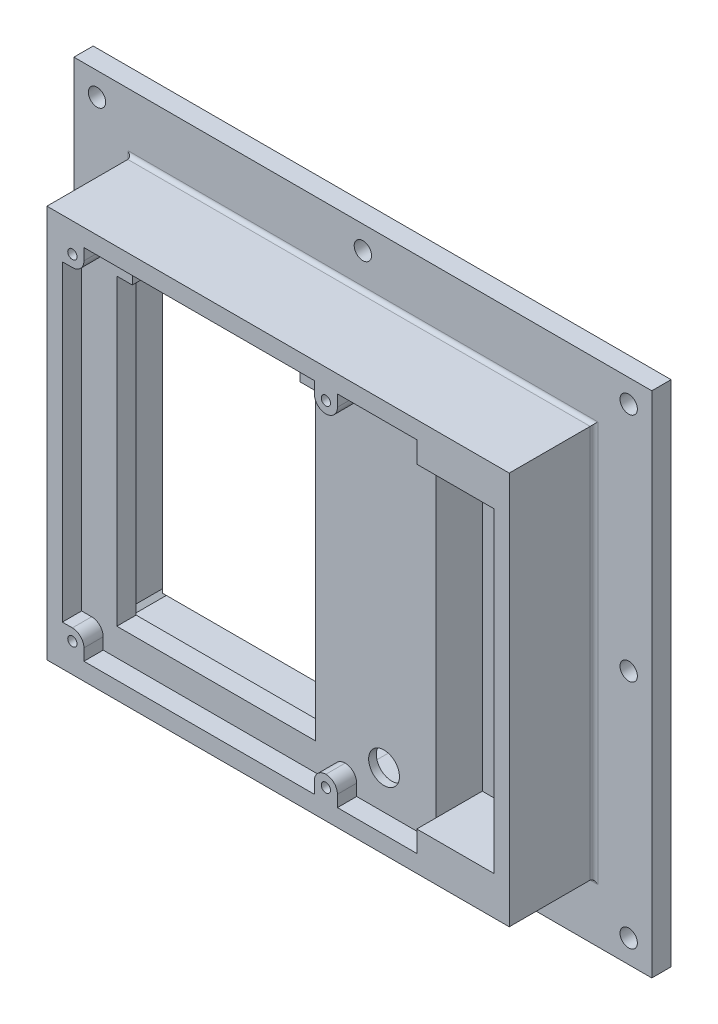
SolidWorks part; units mm, degrees
material "PBT Общее назначение"
ref_plane "Спереди" through (0, 0, 0) normal (0, 0, 1) x (1, 0, 0)
ref_plane "Сверху" through (0, 0, 0) normal (0, 1, 0) x (1, 0, 0)
ref_plane "Справа" through (0, 0, 0) normal (1, 0, 0) x (0, 0, -1)
sketch "Эскиз1" plane through (0, 0, 0) normal (0, 0, 1) x (1, 0, 0)
  line L0 (0, 0) -> (120, 0)
  line L1 (0, 0) -> (0, 102)
  line L2 (120, 0) -> (120, 102)
  line L3 (0, 102) -> (120, 102)
  dimension "D1" = 102
  dimension "D2" = 120
extrude "Бобышка-Вытянуть1" add sketch "Эскиз1" along normal blind 22
sketch "Эскиз2" plane through (0, 0, 22) normal (0, 0, 1) x (1, 0, 0)
  line L0 (4, 98) -> (116, 98)
  line L1 (4, 98) -> (4, 4)
  line L2 (116, 98) -> (116, 4)
  line L3 (4, 4) -> (116, 4)
  line L4 (60, 102) -> (60, 0) construction
  line L5 (120, 102) -> (0, 102) construction
  line L6 (0, 0) -> (120, 0) construction
  line L7 (120, 51) -> (0, 51) construction
  line L8 (120, 0) -> (120, 102) construction
  line L9 (0, 102) -> (0, 0) construction
  line L10 (60, 98) -> (60, 4) construction
  line L11 (116, 51) -> (4, 51) construction
  dimension "D1" = 94
  dimension "D2" = 112
extrude "Вырез-Вытянуть1" cut sketch "Эскиз2" against normal through all
sketch "Эскиз3" plane through (0, 0, 0) normal (0, 0, -1) x (-1, 0, 0)
  line L0 (-135, 117) -> (15, 117)
  line L1 (-135, 117) -> (-135, -15)
  line L2 (15, 117) -> (15, -15)
  line L3 (-135, -15) -> (15, -15)
  line L4 (0, 0) -> (-120, 0) construction
  line L5 (0, 102) -> (0, 0) construction
  line L6 (-120, 0) -> (-120, 102) construction
  line L7 (-120, 102) -> (0, 102) construction
  line L12 (-116, 98) -> (-4, 98) construction
  line L13 (-4, 98) -> (-4, 4) construction
  line L14 (-4, 4) -> (-116, 4) construction
  line L15 (-116, 4) -> (-116, 98) construction
  line L16 (-116, 98) -> (-4, 98)
  line L17 (-4, 98) -> (-4, 4)
  line L18 (-4, 4) -> (-116, 4)
  line L19 (-116, 4) -> (-116, 98)
  dimension "D1" = 15
  dimension "D2" = 15
  dimension "D3" = 15
  dimension "D4" = 15
extrude "Бобышка-Вытянуть2" add sketch "Эскиз3" along normal blind 5
sketch "Эскиз4" plane through (0, 0, 22) normal (0, 0, 1) x (1, 0, 0)
  line L0 (4, 98) -> (116, 98)
  line L1 (4, 98) -> (4, 83)
  line L2 (116, 98) -> (116, 83)
  line L3 (4, 83) -> (116, 83)
  line L4 (4, 19) -> (116, 19)
  line L5 (116, 4) -> (116, 19)
  line L7 (4, 4) -> (4, 19)
  line L8 (4, 98) -> (4, 4) construction
  line L9 (4, 4) -> (116, 4)
  line L12 (116, 51) -> (4, 51) construction
  line L13 (116, 4) -> (116, 98) construction
  dimension "D1" = 15
extrude "Бобышка-Вытянуть3" add sketch "Эскиз4" against normal blind 5
sketch "Эскиз5" plane through (0, 0, -5) normal (0, 0, -1) x (-1, 0, 0)
  line L0 (-60, 117) -> (-60, -15) construction
  line L1 (15, 117) -> (-135, 117) construction
  line L2 (-135, -15) -> (15, -15) construction
  line L3 (-135, 51) -> (15, 51) construction
  line L4 (-135, 117) -> (-135, -15) construction
  line L5 (15, -15) -> (15, 117) construction
ref_plane "Плоскость1" through (60, 0, 0) normal (1, 0, 0) x (0, -1, 0)
ref_plane "Плоскость2" through (0, 51, 0) normal (0, -1, 0) x (-1, 0, 0)
sketch "Эскиз6" plane through (0, 0, 17) normal (0, 0, -1) x (-1, 0, 0)
  line L0 (-4, 98) -> (-4, 83) construction
  line L1 (-116, 98) -> (-4, 98) construction
  line L2 (-4, 4) -> (-116, 4) construction
  line L3 (-4, 19) -> (-4, 4) construction
  line L4 (-6.6, 94.5) -> (-6.6, 7.5) construction
  line L5 (-6.6, 94.5) -> (-72.4, 94.5) construction
  line L6 (-6.6, 7.5) -> (-72.4, 7.5) construction
  line L7 (-72.4, 94.5) -> (-72.4, 7.5) construction
  circle A1 centre (-6.6, 94.5) radius 1.2
  circle A3 centre (-72.4, 94.5) radius 1.2
  circle A5 centre (-6.6, 7.5) radius 1.2
  circle A7 centre (-72.4, 7.5) radius 1.2
  dimension "D1" = 2.6
  dimension "D2" = 3.5
  dimension "D3" = 2.4
  dimension "D4" = 3.5
  dimension "D5" = 2.6
  dimension "D6" = 2.4
  dimension "D7" = 65.8
  dimension "D8" = 2.4
  dimension "D9" = 2.4
extrude "Вырез-Вытянуть2" cut sketch "Эскиз6" against normal through all
fillet "Скругление1" radius 1 4 edges at (60, 0, 0) (120, 51, 0) (60, 102, 0) (0, 51, 0)
sketch "Эскиз7" plane through (0, 0, 0) normal (0, 0, 1) x (1, 0, 0)
  line L0 (-9, -9) -> (-9, 111) construction
  line L1 (-9, -9) -> (129, -9) construction
  line L2 (-9, 111) -> (129, 111) construction
  line L3 (129, -9) -> (129, 111) construction
  line L4 (-15, -15) -> (-15, 117) construction
  line L5 (135, -15) -> (-15, -15) construction
  line L6 (-15, 117) -> (135, 117) construction
  line L7 (135, 117) -> (135, -15) construction
  circle A0 centre (-9, 111) radius 2.25
  circle A1 centre (129, 111) radius 2.25
  circle A2 centre (129, -9) radius 2.25
  circle A3 centre (-9, -9) radius 2.25
  circle A4 centre (-9, 51) radius 2.25
  circle A5 centre (60, 111) radius 2.25
  circle A6 centre (129, 51) radius 2.25
  circle A7 centre (60, -9) radius 2.25
  dimension "D5" = 4.5
  dimension "D6" = 4.5
  dimension "D7" = 4.5
  dimension "D8" = 4.5
  dimension "D9" = 4.5
  dimension "D10" = 4.5
  dimension "D11" = 4.5
  dimension "D12" = 4.5
  dimension "D13" = 60
  dimension "D1" = 6
  dimension "D2" = 6
  dimension "D3" = 6
  dimension "D4" = 6
extrude "Вырез-Вытянуть3" cut sketch "Эскиз7" against normal through all
sketch "Эскиз8" plane through (0, 0, 17) normal (0, 0, -1) x (-1, 0, 0)
  line L0 (-116, 4) -> (-92, 4)
  line L1 (-116, 4) -> (-116, 98)
  line L2 (-92, 4) -> (-92, 98)
  line L3 (-116, 98) -> (-92, 98)
  line L4 (-4, 4) -> (-116, 4) construction
  line L5 (-116, 98) -> (-4, 98) construction
  dimension "D1" = 24
extrude "Бобышка-Вытянуть4" add sketch "Эскиз8" along normal blind 15
sketch "Эскиз9" plane through (0, 0, 22) normal (0, 0, 1) x (1, 0, 0)
  line L1 (92, 19) -> (92, 83) construction
  line L2 (96, 92) -> (116, 92)
  line L3 (92, 19) -> (92, 83) construction
  line L4 (116, 92) -> (116, 10)
  line L5 (96, 10) -> (116, 10)
  line L6 (116, 19) -> (116, 83) construction
  line L7 (120, 102) -> (0, 102) construction
  line L8 (0, 0) -> (120, 0) construction
  line L9 (96, 92) -> (96, 10)
  dimension "D1" = 10
  dimension "D2" = 10
  dimension "D3" = 4
extrude "Вырез-Вытянуть4" cut sketch "Эскиз9" against normal blind 17
sketch "Эскиз10" plane through (0, 0, 2) normal (0, 0, -1) x (-1, 0, 0)
  line L0 (-106, 80) -> (-106, 55) construction
  line L1 (-116, 92) -> (-96, 92) construction
  line L3 (-116, 98) -> (-116, 4) construction
  circle A0 centre (-106, 80) radius 4
  circle A1 centre (-106, 55) radius 4
  dimension "D1" = 8
  dimension "D2" = 8
  dimension "D3" = 12
  dimension "D4" = 25
  dimension "D5" = 10
extrude "Вырез-Вытянуть5" cut sketch "Эскиз10" against normal through all
sketch "Эскиз11" plane through (0, 0, 5) normal (0, 0, 1) x (1, 0, 0)
  line L0 (99.5, 38.5) -> (113, 38.5)
  line L1 (99.5, 38.5) -> (99.5, 20)
  line L2 (113, 38.5) -> (113, 20)
  line L3 (99.5, 20) -> (113, 20)
  line L5 (96, 10) -> (116, 10) construction
  line L6 (116, 10) -> (116, 92) construction
  line L7 (96, 92) -> (96, 10) construction
  dimension "D1" = 18.5
  dimension "D2" = 13.5
  dimension "D3" = 10
  dimension "D4" = 3
  dimension "D5" = 3.5
extrude "Вырез-Вытянуть6" cut sketch "Эскиз11" against normal through all
sketch "Sketch1" plane through (0, 0, 22) normal (0, 0, 1) x (1, 0, 0)
  line L0 (3.6, 10.5) -> (3.6, 91.5)
  line L1 (9.6, 4.5) -> (69.4, 4.5)
  line L2 (9.6, 97.5) -> (69.4, 97.5)
  line L3 (75.4, 10.5) -> (75.4, 91.5)
  line L4 (69.4, 7.5) -> (69.4, 4.5)
  line L5 (72.4, 10.5) -> (75.4, 10.5)
  line L6 (6.6, 10.5) -> (3.6, 10.5)
  line L7 (9.6, 7.5) -> (9.6, 4.5)
  line L8 (6.6, 91.5) -> (3.6, 91.5)
  line L9 (9.6, 94.5) -> (9.6, 97.5)
  line L10 (69.4, 94.5) -> (69.4, 97.5)
  line L11 (72.4, 91.5) -> (75.4, 91.5)
  arc A0 (72.4, 10.5) -> (69.4, 7.5) centre (72.4, 7.5) ccw
  arc A1 (9.6, 7.5) -> (6.6, 10.5) centre (6.6, 7.5) ccw
  arc A2 (6.6, 91.5) -> (9.6, 94.5) centre (6.6, 94.5) ccw
  arc A3 (69.4, 94.5) -> (72.4, 91.5) centre (72.4, 94.5) ccw
  dimension "D1" = 6
  dimension "D2" = 6
  dimension "D3" = 6
  dimension "D4" = 6
extrude "Cut-Extrude1" cut sketch "Sketch1" against normal through all
sketch "Sketch2" plane through (0, 0, 22) normal (0, 0, 1) x (1, 0, 0)
  line L0 (75.4, 97.5) -> (96, 97.5)
  line L1 (75.4, 97.5) -> (75.4, 4.5)
  line L2 (96, 97.5) -> (96, 4.5)
  line L3 (75.4, 4.5) -> (96, 4.5)
  line L4 (75.4, 83) -> (75.4, 91.5) construction
  line L5 (69.4, 97.5) -> (9.6, 97.5) construction
  line L6 (9.6, 4.5) -> (69.4, 4.5) construction
  line L7 (96, 92) -> (96, 83) construction
extrude "Cut-Extrude2" cut sketch "Sketch2" against normal up to surface (5 mm away) up to face at (94, 51, 17)
fillet "Fillet1" radius 3 2 edges at (75.4, 91.5, 19.5) (75.4, 10.5, 19.5)
sketch "Sketch3" plane through (3.6, 0, 0) normal (1, 0, 0) x (0, 0, -1)
  line L4 (-22, 91.5) -> (-22, 10.5)
  line L5 (-22, 10.5) -> (5, 10.5)
  line L6 (5, 10.5) -> (5, 91.5)
  line L7 (5, 91.5) -> (-22, 91.5)
  line L8 (-22, 91.5) -> (-22, 10.5)
  line L9 (-22, 10.5) -> (5, 10.5)
  line L10 (5, 10.5) -> (5, 91.5)
  line L11 (5, 91.5) -> (-22, 91.5)
  dimension "D1" = 0
extrude "Boss-Extrude1" add sketch "Sketch3" along normal up to surface (0.4 mm away) up to face at (4, 94.75, 6)
sketch "Sketch4" plane through (0, 0, 17) normal (0, 0, -1) x (-1, 0, 0)
  line L0 (-4, 98) -> (-4, 4)
  line L1 (-4, 98) -> (-92, 98)
  line L2 (-4, 4) -> (-92, 4)
  line L3 (-92, 98) -> (-92, 4)
  line L4 (-4, 4) -> (-92, 4) construction
extrude "Boss-Extrude2" add sketch "Sketch4" along normal blind 6
sketch "Sketch5" plane through (0, 0, 17) normal (0, 0, 1) x (1, 0, 0)
  line L4 (64.4, 90.1) -> (13.4, 90.1)
  line L5 (64.4, 11.9) -> (64.4, 90.1)
  line L6 (13.4, 11.9) -> (64.4, 11.9)
  line L7 (13.4, 90.1) -> (13.4, 11.9)
  line L8 (64.4, 90.1) -> (13.4, 90.1) construction
  line L9 (64.4, 11.9) -> (64.4, 90.1) construction
  line L10 (13.4, 11.9) -> (64.4, 11.9) construction
  line L11 (13.4, 90.1) -> (13.4, 11.9) construction
  line L12 (17.4, 95.5) -> (17.4, 90.1)
  line L13 (60.4, 95.5) -> (17.4, 95.5)
  line L14 (60.4, 90.1) -> (60.4, 95.5)
  line L15 (17.4, 90.1) -> (60.4, 90.1)
  line L16 (17.4, 95.5) -> (17.4, 90.1) construction
  line L17 (60.4, 95.5) -> (17.4, 95.5) construction
  line L18 (60.4, 90.1) -> (60.4, 95.5) construction
  line L19 (17.4, 90.1) -> (60.4, 90.1) construction
  dimension "D1" = 0
  dimension "D2" = 0
sketch "Sketch6" plane through (0, 0, 17) normal (0, 0, 1) x (1, 0, 0)
  line L0 (13.4, 90.1) -> (13.4, 11.9) construction
  line L1 (64.4, 90.1) -> (13.4, 90.1) construction
  line L2 (13.4, 11.9) -> (64.4, 11.9) construction
  line L3 (64.4, 11.9) -> (64.4, 90.1) construction
  line L4 (13.4, 90.1) -> (13.4, 11.9) construction
  line L5 (64.4, 90.1) -> (13.4, 90.1) construction
  line L6 (13.4, 11.9) -> (64.4, 11.9) construction
  line L7 (64.4, 11.9) -> (64.4, 90.1) construction
  line L8 (13.15, 11.65) -> (13.15, 90.35)
  line L9 (13.15, 11.65) -> (64.65, 11.65)
  line L10 (13.15, 90.35) -> (64.65, 90.35)
  line L11 (64.65, 11.65) -> (64.65, 90.35)
  dimension "D1" = 0.25
  dimension "D2" = 0.25
  dimension "D3" = 0.25
  dimension "D4" = 0.25
extrude "Cut-Extrude3" cut sketch "Sketch6" against normal through all
sketch "Sketch7" plane through (0, 0, 17) normal (0, 0, 1) x (1, 0, 0)
  line L0 (60.4, 95.5) -> (17.4, 95.5) construction
  line L1 (60.4, 90.1) -> (60.4, 95.5) construction
  line L2 (17.4, 95.5) -> (17.4, 90.1) construction
  line L3 (60.4, 95.5) -> (17.4, 95.5) construction
  line L4 (60.4, 90.1) -> (60.4, 95.5) construction
  line L5 (17.4, 95.5) -> (17.4, 90.1) construction
  line L6 (64.65, 90.35) -> (13.15, 90.35) construction
  line L7 (64.65, 90.35) -> (13.15, 90.35) construction
  line L8 (17.15, 90.35) -> (17.15, 95.75)
  line L9 (17.15, 90.35) -> (60.65, 90.35)
  line L10 (17.15, 95.75) -> (60.65, 95.75)
  line L11 (60.65, 90.35) -> (60.65, 95.75)
  dimension "D1" = 0.25
  dimension "D2" = 0.25
  dimension "D3" = 0.25
extrude "Cut-Extrude4" cut sketch "Sketch7" against normal blind 3.5
sketch "Sketch8" plane through (0, 0, 17) normal (0, 0, 1) x (1, 0, 0)
  circle A0 centre (82.5, 14.5) radius 3.35 construction
  circle A1 centre (82.5, 14.5) radius 3.35 construction
  circle A2 centre (82.5, 14.5) radius 4
  dimension "D1" = 8
extrude "Cut-Extrude5" cut sketch "Sketch8" against normal through all
sketch "Sketch9" plane through (0, 0, 11) normal (0, 0, -1) x (-1, 0, 0)
  circle A1 centre (-82.5, 14.5) radius 8.75
  dimension "D1" = 17.5
extrude "Cut-Extrude6" cut sketch "Sketch9" against normal blind 4
sketch "Sketch11" plane through (0, 0, 17) normal (0, 0, 1) x (1, 0, 0)
  circle A0 centre (6.6, 94.5) radius 1.2 construction
  circle A1 centre (6.6, 7.5) radius 1.2
  circle A2 centre (6.6, 7.5) radius 1.2
  circle A3 centre (6.6, 94.5) radius 1.2
  circle A4 centre (72.4, 7.5) radius 1.2 construction
  circle A5 centre (72.4, 7.5) radius 1.2
  circle A7 centre (72.4, 94.5) radius 1.2
  circle A8 centre (72.4, 94.5) radius 1.2
  dimension "D1" = 0
  dimension "D2" = 0
extrude "Cut-Extrude8" cut sketch "Sketch11" against normal blind 5
sketch "Sketch13" plane through (0, 0, -5) normal (0, 0, -1) x (-1, 0, 0)
  circle A0 centre (-82.5, 14.5) radius 4 construction
  circle A1 centre (-82.5, 14.5) radius 4 construction
  circle A2 centre (-82.5, 14.5) radius 13.25
  dimension "D1" = 26.5
extrude "Cut-Extrude9" cut sketch "Sketch13" against normal up to surface (16 mm away) up to face at (73.75, 14.5, 11)
sketch "Sketch14" plane through (0, 0, 2) normal (0, 0, -1) x (-1, 0, 0)
  line L0 (-92, 4) -> (-92, 5.2635) construction
  line L1 (-92, 4) -> (-92, 5.2635)
  line L2 (-92, 4) -> (-90.5816, 4) construction
  line L3 (-92, 4) -> (-90.5816, 4)
  arc A2 (-90.5816, 4) -> (-74.4184, 4) centre (-82.5, 14.5) ccw construction
  arc A3 (-92, 23.7365) -> (-92, 5.2635) centre (-82.5, 14.5) ccw construction
  arc A4 (-90.5816, 4) -> (-74.4184, 4) centre (-82.5, 14.5) ccw construction
  arc A5 (-92, 23.7365) -> (-92, 5.2635) centre (-82.5, 14.5) ccw construction
  arc A6 (-92, 23.7365) -> (-74.4184, 4) centre (-82.5, 14.5) ccw construction
  arc A7 (-92, 5.2635) -> (-90.5816, 4) centre (-82.5, 14.5) ccw
extrude "Boss-Extrude3" add sketch "Sketch14" against normal up to surface (9 mm away) up to face at (68.0937, 29.7812, 11)
fillet "Fillet2" radius 20 2 edges at (92, 23.7365, 6.5) (74.4184, 4, 3)
chamfer "Chamfer1" distance 1 angle 45 12 edges at (73.75, 14.5, 11) (13.15, 51, 11) (38.9, 90.35, 11) (64.65, 51, 11) (38.9, 11.65, 11) (48, 98, 11) (4, 51, 11) (36.6297, 4, 11) (73.3265, 3.5821, 11) (92.1911, 5.4642, 11) (92.5721, 25.0905, 11) (92, 63.9199, 11)
chamfer "Chamfer2" distance 1 angle 45 11 edges at (84.1283, 1.3504, -5) (73.3265, 3.5821, -5) (36.6297, 4, -5) (4, 51, -5) (103.2908, 4, -5) (116, 51, -5) (60, 98, -5) (103.2908, 4, 2) (116, 51, 2) (92, 98, 6) (104, 98, 2)
chamfer "Chamfer4" distance 1 angle 45 4 edges at (116, 4, -1.5) (116, 98, -1.5) (4, 4, 3) (4, 98, 3)
